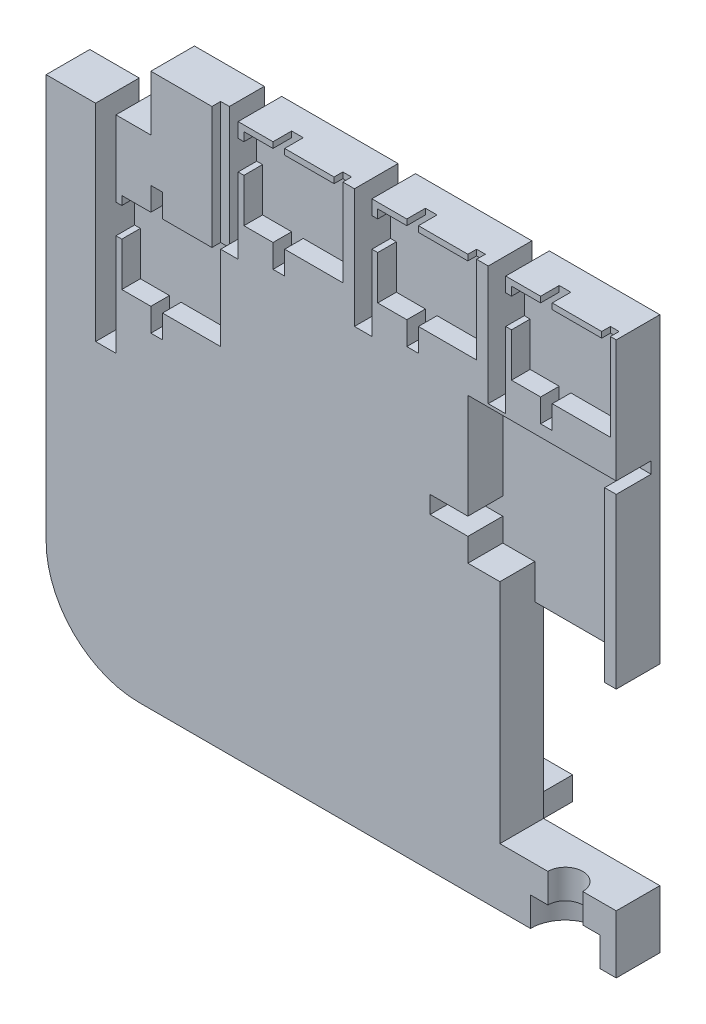
SolidWorks part; units mm, degrees
ref_plane "Front Plane" through (0, 0, 0) normal (0, 0, 1) x (1, 0, 0)
ref_plane "Top Plane" through (0, 0, 0) normal (0, 1, 0) x (1, 0, 0)
ref_plane "Right Plane" through (0, 0, 0) normal (1, 0, 0) x (0, 0, -1)
sketch "Sketch1" plane through (0, 0, 0) normal (0, 0, 1) x (1, 0, 0)
  line L1 (-33, -47.5) -> (49, -47.5)
  line L2 (-49, -31.5) -> (-49, 47.5)
  line L3 (-49, 47.5) -> (27, 47.5)
  line L4 (49, -47.5) -> (49, -29.5)
  line L5 (-49, -47.5) -> (49, 47.5) construction
  line L6 (-49, 47.5) -> (49, -47.5) construction
  line L10 (49, 2.5) -> (31.5, 2.5)
  line L11 (31.5, 2.5) -> (31.5, -29.5)
  line L12 (31.5, -29.5) -> (49, -29.5)
  line L13 (49, 2.5) -> (49, 47.5)
  line L14 (30, 47.5) -> (49, 47.5)
  line L16 (30, 47.5) -> (30, 30.5)
  line L17 (30, 30.5) -> (27, 30.5)
  line L18 (27, 47.5) -> (27, 30.5)
  arc A0 (-33, -47.5) -> (-49, -31.5) centre (-33, -31.5) cw
  point P0 (0, 0)
  point P15 (30, 39)
  dimension "D3" = 16
  dimension "D1" = 98
  dimension "D2" = 95
  dimension "D4" = 18
  dimension "D5" = 17.5
  dimension "D6" = 32
  dimension "D7" = 17
  dimension "D8" = 19
  dimension "D9" = 3
extrude "Boss-Extrude1" add sketch "Sketch1" along normal blind 7.5
sketch "Sketch2" plane through (0, 0, 7.5) normal (0, 0, 1) x (1, 0, 0)
  line L0 (30, 40) -> (31, 40)
  line L1 (30, 47.5) -> (30, 30.5) construction
  line L2 (31, 40) -> (31, 32.5)
  line L3 (31, 32.5) -> (36, 32.5)
  line L4 (36, 32.5) -> (36, 28.5)
  line L5 (36, 28.5) -> (38, 28.5)
  line L6 (38, 28.5) -> (38, 32.5)
  line L7 (38, 32.5) -> (48, 32.5)
  line L8 (48, 32.5) -> (48, 46.5)
  line L9 (48, 46.5) -> (38, 46.5)
  line L10 (31, 46.5) -> (31, 45)
  line L11 (31, 45) -> (30, 45)
  line L12 (30, 45) -> (30, 40)
  line L13 (-16, 40) -> (-15, 40)
  line L14 (36, 46.5) -> (36, 47.5)
  line L15 (49, 47.5) -> (30, 47.5) construction
  line L16 (36, 47.5) -> (38, 47.5)
  line L17 (38, 47.5) -> (38, 46.5)
  line L19 (36, 46.5) -> (31, 46.5)
  line L20 (7, 40) -> (8, 40)
  line L21 (8, 40) -> (8, 32.5)
  line L22 (8, 32.5) -> (13, 32.5)
  line L23 (13, 32.5) -> (13, 28.5)
  line L24 (13, 28.5) -> (15, 28.5)
  line L25 (15, 28.5) -> (15, 32.5)
  line L26 (15, 32.5) -> (25, 32.5)
  line L27 (25, 32.5) -> (25, 46.5)
  line L28 (25, 46.5) -> (15, 46.5)
  line L29 (8, 46.5) -> (8, 45)
  line L30 (8, 45) -> (7, 45)
  line L31 (7, 45) -> (7, 40)
  line L32 (13, 46.5) -> (13, 47.5)
  line L33 (13, 47.5) -> (15, 47.5)
  line L34 (15, 47.5) -> (15, 46.5)
  line L35 (13, 46.5) -> (8, 46.5)
  line L36 (49, 2.5) -> (49, 47.5) construction
  line L37 (27, 47.5) -> (-49, 47.5) construction
  line L38 (-15, 40) -> (-15, 32.5)
  line L39 (-15, 32.5) -> (-10, 32.5)
  line L40 (-10, 32.5) -> (-10, 28.5)
  line L41 (-10, 28.5) -> (-8, 28.5)
  line L42 (-8, 28.5) -> (-8, 32.5)
  line L43 (-8, 32.5) -> (2, 32.5)
  line L44 (2, 32.5) -> (2, 46.5)
  line L45 (2, 46.5) -> (-8, 46.5)
  line L46 (-15, 46.5) -> (-15, 45)
  line L47 (-15, 45) -> (-16, 45)
  line L48 (-16, 45) -> (-16, 40)
  line L49 (-10, 46.5) -> (-10, 47.5)
  line L50 (-10, 47.5) -> (-8, 47.5)
  line L51 (-8, 47.5) -> (-8, 46.5)
  line L52 (-10, 46.5) -> (-15, 46.5)
  point P4 (30, 42.5)
  dimension "D1" = 1
  dimension "D2" = 5
  dimension "D3" = 5
  dimension "D4" = 4
  dimension "D5" = 17
  dimension "D6" = 10
  dimension "D7" = 2
  dimension "D8" = 4
  dimension "D9" = 14
  dimension "D10" = 24
  dimension "D11" = 1
  dimension "D12" = 6
extrude "Cut-Extrude1" cut sketch "Sketch2" against normal blind 3.2
sketch "Sketch3" plane through (0, -47.5, 0) normal (0, -1, 0) x (1, 0, 0)
  line L0 (-33, 7.5) -> (49, 7.5) construction
  line L2 (49, 7.5) -> (31.5, 7.5) construction
  line L4 (34.25, 7.5) -> (46.25, 7.5)
  arc A0 (46.25, 7.5) -> (34.25, 7.5) centre (40.25, 7.5) cw
  point P6 (40.25, 7.5)
  dimension "D2" = 6
  dimension "D1" = 17.5
sketch "Sketch5" plane through (0, 0, 7.5) normal (0, 0, 1) x (1, 0, 0)
  line L0 (7, 47.5) -> (7, 30.5)
  line L1 (13, 47.5) -> (-8, 47.5) construction
  line L2 (7, 30.5) -> (4, 30.5)
  line L3 (4, 30.5) -> (4, 47.5)
  line L4 (4, 47.5) -> (7, 47.5)
  line L5 (27, 30.5) -> (27, 47.5) construction
  line L6 (30, 30.5) -> (27, 30.5) construction
  line L7 (7, 45) -> (7, 40) construction
  line L8 (-16, 47.5) -> (-16, 30.5)
  line L9 (-10, 47.5) -> (-49, 47.5) construction
  line L10 (-16, 30.5) -> (-19, 30.5)
  line L11 (-19, 30.5) -> (-19, 47.5)
  line L12 (-19, 47.5) -> (-16, 47.5)
  line L13 (-16, 45) -> (-16, 40) construction
extrude "Cut-Extrude4" cut sketch "Sketch5" against normal up to next
sketch "Sketch8" plane through (0, 0, 7.5) normal (0, 0, 1) x (1, 0, 0)
  line L0 (-19, 47.5) -> (-49, 47.5) construction
  line L1 (-37, 47.5) -> (-49, 47.5)
  line L2 (-37, 47.5) -> (-37, 10.5)
  line L3 (-37, 10.5) -> (-49, 10.5)
  line L4 (-49, 47.5) -> (-49, 10.5)
  line L5 (-49, 47.5) -> (-49, -31.5) construction
  dimension "D1" = 12
  dimension "D2" = 37
extrude "Cut-Extrude5" cut sketch "Sketch8" against normal up to next
sketch "Sketch9" plane through (0, 0, 7.5) normal (0, 0, 1) x (1, 0, 0)
  line L0 (-37, 20) -> (-36, 20)
  line L1 (-36, 20) -> (-36, 12.5)
  line L2 (-36, 12.5) -> (-31, 12.5)
  line L3 (-31, 12.5) -> (-31, 8.5)
  line L4 (-31, 8.5) -> (-29, 8.5)
  line L5 (-29, 8.5) -> (-29, 12.5)
  line L6 (-29, 12.5) -> (-19, 12.5)
  line L7 (-19, 12.5) -> (-19, 26.5)
  line L8 (-19, 26.5) -> (-29, 26.5)
  line L9 (-36, 26.5) -> (-36, 25)
  line L10 (-36, 25) -> (-37, 25)
  line L11 (-37, 25) -> (-37, 20)
  line L12 (-31, 26.5) -> (-31, 30.5)
  line L13 (-31, 30.5) -> (-29, 30.5)
  line L14 (-29, 30.5) -> (-29, 26.5)
  line L15 (-31, 26.5) -> (-36, 26.5)
  line L16 (-49, 10.5) -> (-37, 10.5) construction
  line L17 (-37, 10.5) -> (-37, 47.5) construction
  point P2 (-37, 22.5)
  dimension "D1" = 14
  dimension "D2" = 17
  dimension "D3" = 10
  dimension "D4" = 2
  dimension "D5" = 5
  dimension "D6" = 4
  dimension "D7" = 7.5
  dimension "D8" = 5
  dimension "D9" = 1
  dimension "D10" = 4
  dimension "D11" = 12
extrude "Cut-Extrude6" cut sketch "Sketch9" against normal blind 3.2
sketch "Sketch10" plane through (0, 10.5, 0) normal (0, 1, 0) x (1, 0, 0)
  line L0 (-49, -7.5) -> (-37, -7.5) construction
  line L1 (-49, 0) -> (-39, 0)
  line L2 (-49, 0) -> (-49, -7.5)
  line L3 (-49, -7.5) -> (-39, -7.5)
  line L4 (-39, 0) -> (-39, -7.5)
  dimension "D1" = 10
extrude "Boss-Extrude2" add sketch "Sketch10" along normal blind 27.4864
sketch "Sketch11" plane through (0, 30.5, 0) normal (0, 1, 0) x (1, 0, 0)
  line L1 (-19, 0) -> (-16, 0)
  line L2 (-19, 0) -> (-19, -7.5)
  line L3 (-19, -7.5) -> (-16, -7.5)
  line L4 (-16, 0) -> (-16, -7.5)
  line L5 (4, 0) -> (7, 0)
  line L6 (4, 0) -> (4, -7.5)
  line L7 (4, -7.5) -> (7, -7.5)
  line L8 (7, 0) -> (7, -7.5)
  line L9 (27, 0) -> (30, 0)
  line L10 (27, 0) -> (27, -7.5)
  line L11 (27, -7.5) -> (30, -7.5)
  line L12 (30, 0) -> (30, -7.5)
extrude "Cut-Extrude7" cut sketch "Sketch11" against normal blind 3.5
sketch "Sketch12" plane through (0, 10.5, 0) normal (0, 1, 0) x (1, 0, 0)
  line L1 (-37, 0) -> (-39, 0)
  line L2 (-37, 0) -> (-37, -7.5)
  line L3 (-37, -7.5) -> (-39, -7.5)
  line L4 (-39, 0) -> (-39, -7.5)
extrude "Cut-Extrude8" cut sketch "Sketch12" against normal blind 4
sketch "Sketch13" plane through (0, 6.5, 0) normal (0, 1, 0) x (1, 0, 0)
  line L1 (-39, 0) -> (-37, 0)
  line L2 (-39, 0) -> (-39, -7.5)
  line L3 (-39, -7.5) -> (-37, -7.5)
  line L4 (-37, 0) -> (-37, -7.5)
extrude "Cut-Extrude9" cut sketch "Sketch13" against normal blind 4
sketch "Sketch14" plane through (-37, 0, 0) normal (-1, 0, 0) x (0, 0, 1)
  line L0 (7.5, 25) -> (7.5, 47.5) construction
  line L1 (0, 47.5) -> (7.5, 47.5)
  line L2 (0, 47.5) -> (0, 38)
  line L3 (0, 38) -> (7.5, 38)
  line L4 (7.5, 47.5) -> (7.5, 38)
  dimension "D1" = 13
extrude "Cut-Extrude10" cut sketch "Sketch14" against normal blind 6
sketch "Sketch15" plane through (0, 0, 7.5) normal (0, 0, 1) x (1, 0, 0)
  line L0 (-19, 26.5) -> (-29, 26.5) construction
  line L1 (-19, 47.5) -> (-20.5, 47.5)
  line L2 (-19, 47.5) -> (-19, 26.5)
  line L3 (-19, 26.5) -> (-20.5, 26.5)
  line L4 (-20.5, 47.5) -> (-20.5, 26.5)
  line L5 (4, 47.5) -> (-8, 47.5) construction
  line L6 (2, 46.5) -> (0.5, 46.5)
  line L7 (2, 46.5) -> (2, 47.5)
  line L8 (2, 47.5) -> (0.5, 47.5)
  line L9 (0.5, 46.5) -> (0.5, 47.5)
  line L10 (27, 47.5) -> (15, 47.5) construction
  line L11 (25, 46.5) -> (23.5, 46.5)
  line L12 (25, 46.5) -> (25, 47.5)
  line L13 (25, 47.5) -> (23.5, 47.5)
  line L14 (23.5, 46.5) -> (23.5, 47.5)
  line L15 (49, 47.5) -> (38, 47.5) construction
  line L16 (48, 46.5) -> (46.5, 46.5)
  line L17 (48, 46.5) -> (48, 47.5)
  line L18 (48, 47.5) -> (46.5, 47.5)
  line L19 (46.5, 46.5) -> (46.5, 47.5)
  dimension "D1" = 1.5
  dimension "D2" = 1.5
  dimension "D3" = 1.5
  dimension "D4" = 1.5
extrude "Cut-Extrude11" cut sketch "Sketch15" against normal blind 1.5
ref_plane "Plane1" through (0, 0, 17.5) normal (0, 0, 1) x (1, 0, 0)
sketch "Sketch16" plane through (0, 37.9864, 0) normal (0, 1, 0) x (1, 0, 0)
  line L0 (-39, 0) -> (-49, 0) construction
  line L1 (-40.5, 0) -> (-39, 0)
  line L2 (-40.5, 0) -> (-40.5, -7.5)
  line L3 (-40.5, -7.5) -> (-39, -7.5)
  line L4 (-39, 0) -> (-39, -7.5)
  line L5 (-49, -7.5) -> (-39, -7.5) construction
  line L6 (-49, 0) -> (-49, -7.5) construction
  dimension "D1" = 8.5
  dimension "D2" = 10
extrude "Cut-Extrude12" cut sketch "Sketch16" against normal blind 35.4864
sketch "Sketch18" plane through (0, 0, 7.5) normal (0, 0, 1) x (1, 0, 0)
  line L0 (23.5, 5.5) -> (23.5, 1.5)
  line L1 (23.5, 26.5) -> (47, 26.5)
  line L2 (23.5, 26.5) -> (23.5, 8.5)
  line L3 (23.5, 1.5) -> (47, 1.5)
  line L4 (47, 24.5) -> (47, 1.5)
  line L5 (23.5, 5.5) -> (17, 5.5)
  line L7 (23.5, 8.5) -> (17, 8.5)
  line L8 (17, 5.5) -> (17, 8.5)
  line L9 (49, 2.5) -> (49, 47.5) construction
  line L11 (27, 27) -> (30, 27) construction
  line L12 (47, 26.5) -> (49, 26.5)
  line L14 (47, 24.5) -> (49, 24.5)
  line L15 (49, 26.5) -> (49, 24.5)
  point P5 (23.5, 5.5)
  dimension "D1" = 23.5
  dimension "D2" = 25
  dimension "D3" = 4
  dimension "D4" = 6.5
  dimension "D5" = 3
  dimension "D6" = 2
  dimension "D7" = 2
  dimension "D8" = 23.5
  dimension "D9" = 0.5
extrude "Cut-Extrude13" cut sketch "Sketch18" against normal blind 6
sketch "Sketch19" plane through (0, 0, 0) normal (0, 0, -1) x (-1, 0, 0)
  line L1 (-31.5, 2.5) -> (-49, 2.5)
  line L2 (-31.5, 2.5) -> (-31.5, -29.5)
  line L3 (-31.5, -29.5) -> (-49, -29.5)
  line L4 (-49, 2.5) -> (-49, -29.5)
extrude "Boss-Extrude3" add sketch "Sketch19" against normal blind 7.5 contours L2 L1 L4 L3
extrude "Cut-Extrude14" cut sketch "Sketch18<2>" against normal blind 6
sketch "Sketch18<2>" plane through (0, 0, 7.5) normal (0, 0, 1) x (1, 0, 0) same geometry as "Sketch18"
sketch "Sketch20" plane through (0, 0, 7.5) normal (0, 0, 1) x (1, 0, 0)
  line L0 (47, 1.5) -> (29, 1.5)
  line L5 (23.5, 1.5) -> (47, 1.5) construction
  line L6 (47, 1.5) -> (47, -4.5)
  line L7 (47, -4.5) -> (29, -4.5)
  line L8 (29, -4.5) -> (29, 1.5)
  dimension "D1" = 18
  dimension "D2" = 6
extrude "Cut-Extrude15" cut sketch "Sketch20" against normal blind 6
sketch "Sketch21" plane through (0, 0, 7.5) normal (0, 0, 1) x (1, 0, 0)
  line L0 (49, -4.5) -> (49, -37.5)
  line L1 (49, -47.5) -> (49, 24.5) construction
  line L2 (49, -37.5) -> (29, -37.5)
  line L3 (29, -37.5) -> (29, -4.5)
  line L4 (29, -4.5) -> (49, -4.5)
  line L6 (29, -4.5) -> (47, -4.5) construction
  dimension "D1" = 33
  dimension "D2" = 20
extrude "Cut-Extrude16" cut sketch "Sketch21" against normal blind 11
extrude "Cut-Extrude17" cut sketch "Sketch3" against normal blind 5
sketch "Sketch22" plane through (0, -42.5, 0) normal (0, -1, 0) x (1, 0, 0)
  line L0 (46.25, 7.5) -> (34.25, 7.5) construction
  line L1 (37.25, 7.5) -> (43.25, 7.5)
  arc A0 (37.25, 7.5) -> (43.25, 7.5) centre (40.25, 7.5) ccw
  dimension "D1" = 3
extrude "Cut-Extrude18" cut sketch "Sketch22" against normal blind 10
sketch "Sketch23" plane through (0, 0, 0) normal (0, 0, -1) x (-1, 0, 0)
  line L0 (33, -47.5) -> (-49, -47.5) construction
  line L1 (-19, -47.5) -> (31, -47.5)
  line L2 (-19, -47.5) -> (-19, -43.5)
  line L3 (-19, -43.5) -> (31, -43.5)
  line L4 (31, -47.5) -> (31, -43.5)
  line L5 (-49, -47.5) -> (-49, -37.5) construction
  dimension "D1" = 4
  dimension "D2" = 50
  dimension "D3" = 30
extrude "Boss-Extrude4" add sketch "Sketch23" along normal blind 15
sketch "Sketch24" plane through (0, -43.5, 0) normal (0, 1, 0) x (1, 0, 0)
  line L0 (2.3333, 7.5) -> (2.3333, 15) construction
  line L1 (-31, 15) -> (19, 15) construction
  line L2 (2.3333, 7.5) -> (2.3333, 0) construction
  line L3 (-31, 0) -> (19, 0) construction
  line L4 (19, 7.5) -> (2.3333, 7.5) construction
  line L5 (19, 15) -> (19, 0) construction
  line L6 (2.3333, 7.5) -> (-14.3333, 7.5) construction
  line L7 (-14.3333, 7.5) -> (-31, 7.5) construction
  line L8 (-31, 15) -> (-31, 0) construction
  circle A0 centre (2.3333, 7.5) radius 0.5
  circle A1 centre (-14.3333, 7.5) radius 0.5
  dimension "D1" = 1
sketch "Sketch25" plane through (0, -47.5, 0) normal (0, -1, 0) x (-1, 0, 0)
  line L0 (49, -7.5) -> (49, 0) construction
  line L1 (33, -7.5) -> (-34.25, -7.5) construction
  circle A0 centre (-1, 7.5) radius 3.5
  dimension "D2" = 7
  dimension "D1" = 50
  dimension "D3" = 15
extrude "Cut-Extrude19" cut sketch "Sketch25" against normal blind 10
ref_plane "Plane2" through (0, 0, 17.5) normal (0, 0, 1) x (1, 0, 0)
